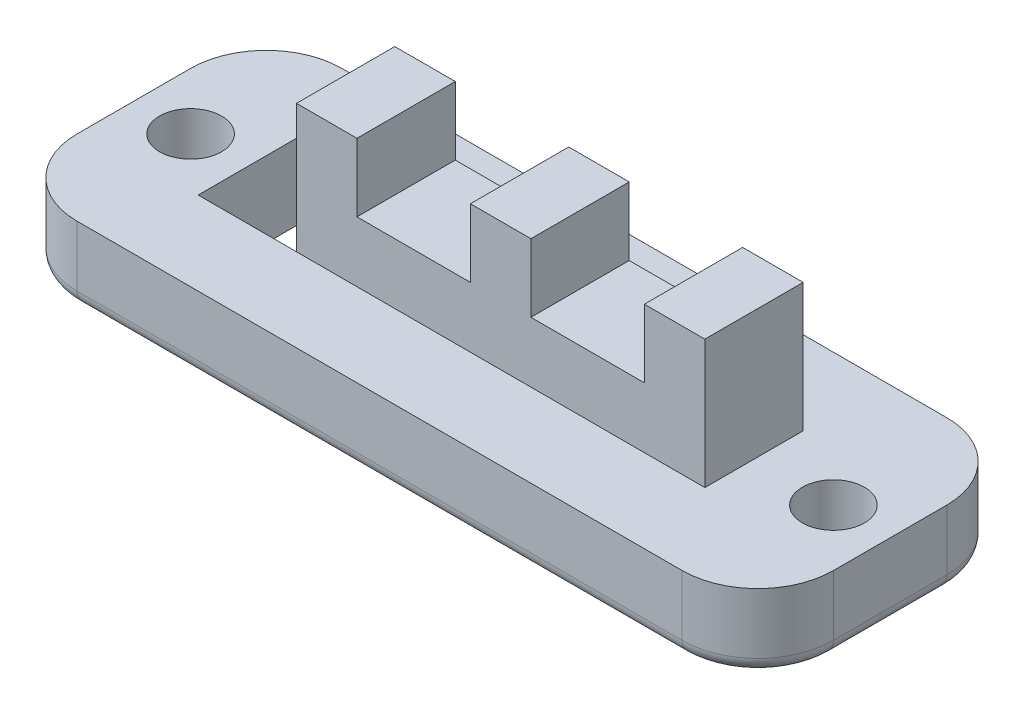
SolidWorks part; units mm, degrees
ref_plane "Front Plane" through (0, 0, 0) normal (0, 0, 1) x (1, 0, 0)
ref_plane "Top Plane" through (0, 0, 0) normal (0, 1, 0) x (1, 0, 0)
ref_plane "Right Plane" through (0, 0, 0) normal (1, 0, 0) x (0, 0, -1)
sketch "Sketch1" plane through (0, 0, 0) normal (0, 1, 0) x (1, 0, 0)
  line L1 (-12.7, -4.445) -> (12.7, -4.445)
  line L2 (-12.7, -4.445) -> (-12.7, 4.445)
  line L3 (-12.7, 4.445) -> (12.7, 4.445)
  line L4 (12.7, -4.445) -> (12.7, 4.445)
  line L5 (-12.7, -4.445) -> (12.7, 4.445) construction
  line L6 (-12.7, 4.445) -> (12.7, -4.445) construction
  point P0 (0, 0)
  dimension "D1" = 25.4
  dimension "D2" = 8.89
extrude "Boss-Extrude1" add sketch "Sketch1" along normal blind 2.54
sketch "Sketch2" plane through (0, 2.54, 0) normal (0, 1, 0) x (1, 0, 0)
  line L0 (12.7, 4.445) -> (-12.7, 4.445) construction
  line L1 (-8.89, -1.651) -> (8.128, -1.651)
  line L2 (-8.89, -1.651) -> (-8.89, 1.651)
  line L3 (-8.89, 1.651) -> (8.128, 1.651)
  line L4 (8.128, -1.651) -> (8.128, 1.651)
  line L5 (-12.7, 4.445) -> (-12.7, -4.445) construction
  line L6 (12.7, -4.445) -> (12.7, 4.445) construction
  line L7 (-12.7, -4.445) -> (12.7, -4.445) construction
  point P0 (0, 0)
  dimension "D1" = 2.794
  dimension "D2" = 3.81
  dimension "D3" = 4.572
  dimension "D4" = 2.794
extrude "Boss-Extrude2" add sketch "Sketch2" along normal blind 2.032
sketch "Sketch3" plane through (0, 0, 0) normal (0, -1, 0) x (1, 0, 0)
  line L0 (-12.7, -4.445) -> (-12.7, 4.445) construction
  line L1 (12.7, 4.445) -> (12.7, -4.445) construction
  circle A0 centre (-10.795, 0) radius 1.0414
  circle A1 centre (10.795, 0) radius 1.0414
  point P6 (-12.7, 0)
extrude "Cut-Extrude1" cut sketch "Sketch3" against normal through all
sketch "Sketch4" plane through (0, 4.572, 0) normal (0, 1, 0) x (1, 0, 0)
  line L0 (8.128, 1.651) -> (-8.89, 1.651) construction
  line L1 (-8.89, -1.651) -> (-5.588, -1.651)
  line L2 (-8.89, -1.651) -> (-8.89, 1.651)
  line L3 (-8.89, 1.651) -> (-5.588, 1.651)
  line L4 (-5.588, -1.651) -> (-5.588, 1.651)
  dimension "D1" = 3.302
extrude "Cut-Extrude2" cut sketch "Sketch4" against normal up to surface (4.572 mm away) up to face at (-10.795, 0, -1.0414)
sketch "Sketch5" plane through (0, 4.572, 0) normal (0, 1, 0) x (1, 0, 0)
  line L0 (8.128, 1.651) -> (-5.588, 1.651) construction
  line L1 (-5.588, 1.651) -> (-3.556, 1.651)
  line L2 (-5.588, 1.651) -> (-5.588, -1.651)
  line L3 (-5.588, -1.651) -> (-3.556, -1.651)
  line L4 (-3.556, 1.651) -> (-3.556, -1.651)
  line L5 (-5.588, -1.651) -> (8.128, -1.651) construction
  line L6 (-5.588, -1.651) -> (-5.588, 1.651) construction
  line L7 (8.128, 1.651) -> (-5.588, 1.651) construction
  line L8 (0.254, 1.651) -> (2.286, 1.651)
  line L9 (0.254, 1.651) -> (0.254, -1.651)
  line L10 (0.254, -1.651) -> (2.286, -1.651)
  line L11 (2.286, 1.651) -> (2.286, -1.651)
  line L12 (8.128, -1.651) -> (8.128, 1.651) construction
  line L18 (6.096, 1.651) -> (8.128, 1.651)
  line L19 (6.096, 1.651) -> (6.096, -1.651)
  line L20 (6.096, -1.651) -> (8.128, -1.651)
  line L21 (8.128, 1.651) -> (8.128, -1.651)
  dimension "D2" = 2.032
  dimension "D4" = 2.032
  dimension "D1" = 2.032
  dimension "D3" = 3.81
sketch "Sketch6" plane through (0, 4.572, 0) normal (0, 1, 0) x (1, 0, 0)
  line L0 (8.128, 1.651) -> (-5.588, 1.651) construction
  line L1 (-1.27, 1.651) -> (0.762, 1.651)
  line L2 (-1.27, 1.651) -> (-1.27, -1.651)
  line L3 (-1.27, -1.651) -> (0.762, -1.651)
  line L4 (0.762, 1.651) -> (0.762, -1.651)
  line L5 (-5.588, -1.651) -> (8.128, -1.651) construction
  line L6 (-3.556, 1.651) -> (-3.556, -1.651) construction
  line L8 (8.128, 1.651) -> (-5.588, 1.651) construction
  line L9 (3.048, 1.651) -> (8.128, 1.651)
  line L10 (3.048, 1.651) -> (3.048, -1.651)
  line L11 (3.048, -1.651) -> (8.128, -1.651)
  line L12 (8.128, 1.651) -> (8.128, -1.651)
  dimension "D1" = 2.032
  dimension "D2" = 2.286
  dimension "D3" = 2.286
extrude "Boss-Extrude3" add sketch "Sketch5" along normal blind 2.286
fillet "Fillet1" radius 2.54 4 edges at (12.7, 1.27, 4.445) (12.7, 1.27, -4.445) (-12.7, 1.27, 4.445) (-12.7, 1.27, -4.445)
fillet "Fillet2" radius 0.508 8 edges at (-11.9561, 0, 3.7011) (-12.7, 0, 0) (-11.9561, 0, -3.7011) (0, 0, -4.445) (11.9561, 0, -3.7011) (12.7, 0, 0) (11.9561, 0, 3.7011) (0, 0, 4.445)
equation "\"D2@Sketch3\"=\"D1@Sketch3\""
equation "\"D4@Sketch5\"=\"D2@Sketch5\""
equation "\"D1@Sketch5\"=\"D2@Sketch5\""
equation "\"D4@Sketch2\"=\"D1@Sketch2\""
